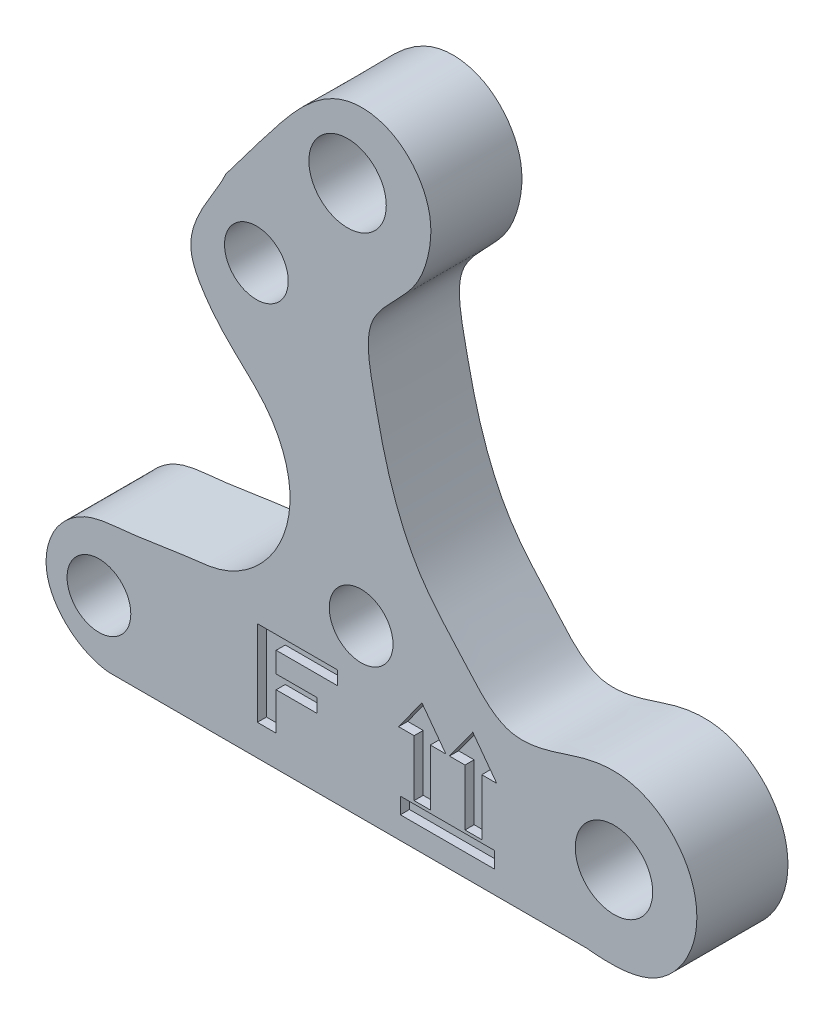
SolidWorks part; units mm, degrees
ref_plane "Piano frontale" through (0, 0, 0) normal (0, 0, 1) x (1, 0, 0)
ref_plane "Piano superiore" through (0, 0, 0) normal (0, 1, 0) x (1, 0, 0)
ref_plane "Piano destro" through (0, 0, 0) normal (1, 0, 0) x (0, 0, -1)
sketch "Model" plane through (0, 0, 0) normal (0, 0, 1) x (1, 0, 0)
  line L0 (22.0868, -27.7982) -> (-30.3742, -27.7982)
  line L1 (-13.8722, 30.8613) -> (-17.5384, 26.0041)
  line L3 (-12.014, -24.4034) -> (-12.014, -20.2736)
  line L4 (-12.014, -20.2736) -> (-7.5087, -20.2736)
  line L5 (-7.5087, -20.2736) -> (-7.5087, -18.7718)
  line L6 (-7.5087, -18.7718) -> (-12.014, -18.7718)
  line L7 (-12.014, -18.7718) -> (-12.014, -16.5192)
  line L8 (-12.014, -16.5192) -> (-5.2561, -16.5192)
  line L9 (-5.2561, -16.5192) -> (-5.2561, -15.0175)
  line L10 (-5.2561, -15.0175) -> (-14.0789, -15.0175)
  line L11 (-14.0789, -15.0175) -> (-14.0789, -24.4034)
  line L12 (-14.0789, -24.4034) -> (-12.014, -24.4034)
  line L13 (11.9389, -25.342) -> (11.9389, -23.568)
  line L14 (11.9389, -23.568) -> (1.6238, -23.568)
  line L15 (1.6238, -23.568) -> (1.6238, -25.342)
  line L16 (1.6238, -25.342) -> (11.9389, -25.342)
  line L17 (3.1349, -17.0636) -> (3.1349, -23.2395)
  line L18 (3.1349, -23.2395) -> (4.9088, -23.2395)
  line L19 (4.9088, -23.2395) -> (4.9088, -17.0636)
  line L20 (4.9088, -17.0636) -> (6.6171, -17.0636)
  line L21 (6.6171, -17.0636) -> (3.989, -13.5157)
  line L22 (3.989, -13.5157) -> (1.4267, -17.0636)
  line L23 (1.4267, -17.0636) -> (3.1349, -17.0636)
  line L24 (8.7195, -17.0636) -> (8.7195, -23.2395)
  line L25 (8.7195, -23.2395) -> (10.5592, -23.2395)
  line L26 (10.5592, -23.2395) -> (10.5592, -17.0636)
  line L27 (10.5592, -17.0636) -> (12.2017, -17.0636)
  line L28 (12.2017, -17.0636) -> (9.5736, -13.5157)
  line L29 (9.5736, -13.5157) -> (7.0113, -17.0636)
  line L30 (7.0113, -17.0636) -> (8.7195, -17.0636)
  line L33 (-14.1862, 19.2414) -> (-2.6848, -9.5461) construction
  line L34 (-14.1862, 19.2414) -> (-42.9737, 7.74) construction
  line L35 (-2.6848, -9.5461) -> (-31.4723, -21.0474) construction
  line L36 (-42.9737, 7.74) -> (-31.4723, -21.0474) construction
  circle A0 centre (-31.4723, -21.0474) radius 3.5
  circle A1 centre (-31.4723, -21.0474) radius 1.75
  circle A2 centre (25.0764, -18.8492) radius 4.25
  circle A3 centre (-4.1736, 31.8132) radius 4.25
  circle A4 centre (-14.1862, 19.2414) radius 3.5
  circle A5 centre (-14.1862, 19.2414) radius 1.75
  circle A6 centre (-2.6848, -9.5461) radius 3.5
  circle A7 centre (-2.6848, -9.5461) radius 1.75
  spline S0 degree 3 poles (-17.5384, 26.0041) (-18.5383, 23.6059) (-22.9066, 18.7541) (-19.9898, 13.3732) (-17.0183, 9.6824) (-12.1971, 5.9861) (-9.6734, -1.214) (-12.0562, -8.3476) (-17.1104, -12.0777) (-21.535, -12.4287) (-24.918, -12.9763) (-28.5888, -13.5171) (-32.9532, -13.7948) (-36.7404, -16.8305) (-38.1891, -23.6168) (-33.4872, -27.5208) (-30.3742, -27.7982) knots 0 0 0 0 0.128042 0.173454 0.219153 0.309797 0.399283 0.488821 0.578317 0.618189 0.656227 0.708612 0.759756 0.819423 0.878795 1 1 1 1
  spline S1 degree 3 poles (-13.8722, 30.8613) (-11.2429, 34.1378) (-7.15, 40.5202) (1.5622, 39.4164) (5.3459, 34.5588) (4.8684, 29.2717) (2.8695, 24.3539) (-2.7703, 20.7069) (-1.1921, 12.6631) (0.3338, 5.6041) (3.5533, -1.8737) (8.439, -6.9293) (12.7007, -12.1075) (18.0194, -11.2219) (21.8807, -9.6806) (26.2361, -9.1685) (30.7504, -10.9935) (34.1244, -15.3044) (34.5217, -21.8166) (29.9397, -28.1652) (24.4483, -28.0456) (22.0868, -27.7982) knots 0 0 0 0 0.113777 0.147278 0.205992 0.245683 0.275494 0.337832 0.391118 0.459762 0.52599 0.587795 0.640879 0.676387 0.7119 0.747233 0.782557 0.829334 0.876114 0.937741 1 1 1 1
  point P0 (25.0764, -18.8492)
  dimension "D4" = 8.5
  dimension "D5" = 3.5
  dimension "D6" = 7
  dimension "D1" = 8.5
  dimension "D3" = 31
extrude "Main body" add sketch "Model" against normal blind 10 contours S0 L0 S1 L1 | A5 | A3 | A7 | A1 | A2
extrude "Symbols" cut sketch "Model<5>" against normal blind 1 contours L11 L12 L3 L4 L5 L6 L7 L8 L9 L10 | L22 L23 L17 L18 L19 L20 L21 | L15 L16 L13 L14 | L29 L30 L24 L25 L26 L27 L28 region at (-13.0464, -24.2746, 0) region at (6.7813, -24.455, 0) region at (4.0169, -18.2014, 0) region at (9.6197, -18.2399, 0)
sketch "Model<5>" plane through (0, 0, 0) normal (0, 0, 1) x (1, 0, 0) same geometry as "Model"
extrude "Recess holes" cut sketch "Model<6>" against normal blind 6 contours A4 A5 | A0 A1 | A6 A7 | A0 A1 | A6 A7 | A4 A5 region at (-34.8733, -21.0474, 0) region at (-17.5872, 19.2414, 0) region at (-6.0859, -9.5461, 0)
sketch "Model<6>" plane through (0, 0, 0) normal (0, 0, 1) x (1, 0, 0) same geometry as "Model"
ref_axis "Rod1 axis" through (-4.1736, 31.8132, -10) along (0, 0, 1)
ref_axis "Motor screw 1" through (-31.4723, -21.0474, -10) along (0, 0, 1)
ref_axis "Motor screw 2" through (-2.6848, -9.5461, -10) along (0, 0, 1)
ref_axis "Motor screw 3" through (-14.1862, 19.2414, -10) along (0, 0, 1)
